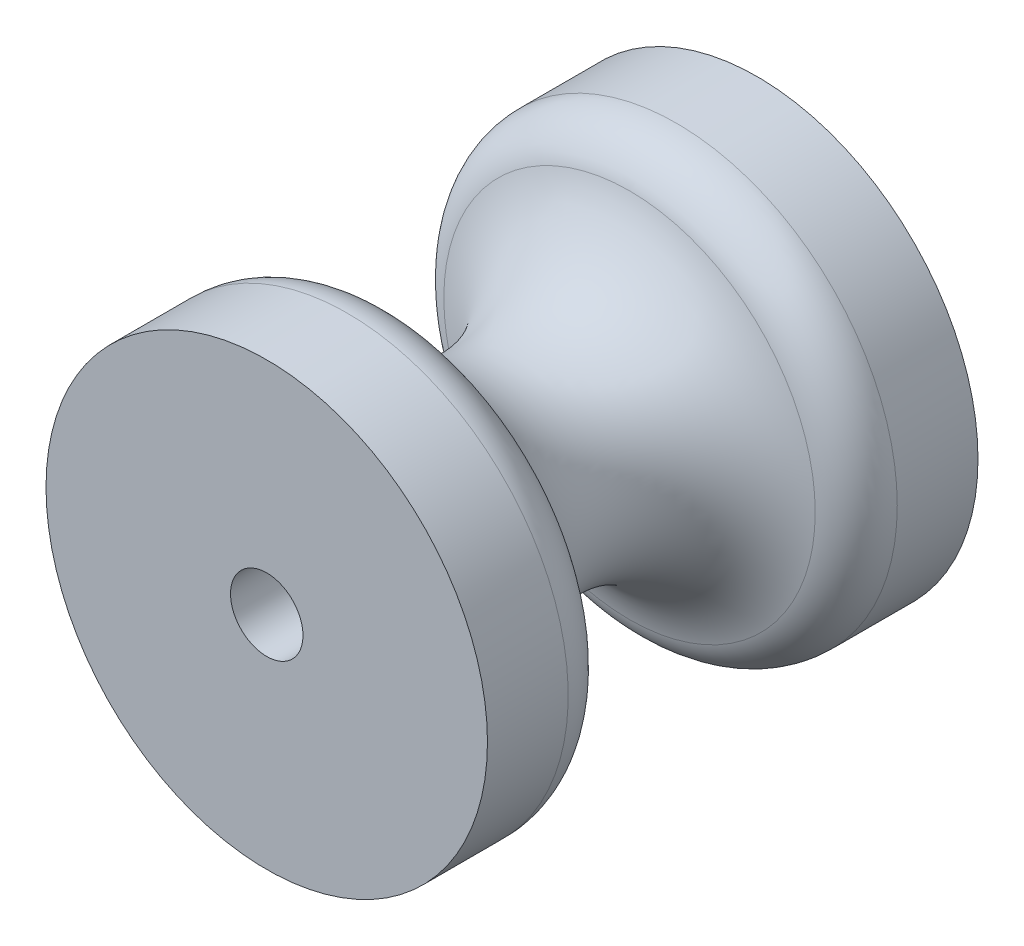
SolidWorks part; units mm, degrees
ref_plane "Front Plane" through (0, 0, 0) normal (0, 0, 1) x (1, 0, 0)
ref_plane "Top Plane" through (0, 0, 0) normal (0, 1, 0) x (1, 0, 0)
ref_plane "Right Plane" through (0, 0, 0) normal (1, 0, 0) x (0, 0, -1)
sketch "Sketch1" plane through (0, 0, 0) normal (0, 0, 1) x (1, 0, 0)
  circle A0 centre (0, 0) radius 90
  dimension "D1" = 180
extrude "Boss-Extrude1" add sketch "Sketch1" along normal blind 200
sketch "Sketch2" plane through (0, 0, 0) normal (1, 0, 0) x (0, 0, -1)
  line L0 (0, 90) -> (-200, 90) construction
  circle A0 centre (-100, 90) radius 50
  dimension "D1" = 100
ref_axis "Axis1" through (0, 0, -10) along (0, 0, 1)
revolve "Cut-Revolve1" cut sketch "Sketch2" angle 360 about axis through (0, 0, -10) along (0, 0, 1)
fillet "Fillet1" radius 20 2 edges at (-90, 0, 150) (90, 0, 50)
sketch "Sketch3" plane through (0, 0, 200) normal (0, 0, 1) x (1, 0, 0)
  circle A0 centre (0, 0) radius 14.776
extrude "Cut-Extrude1" cut sketch "Sketch3" against normal blind 500
